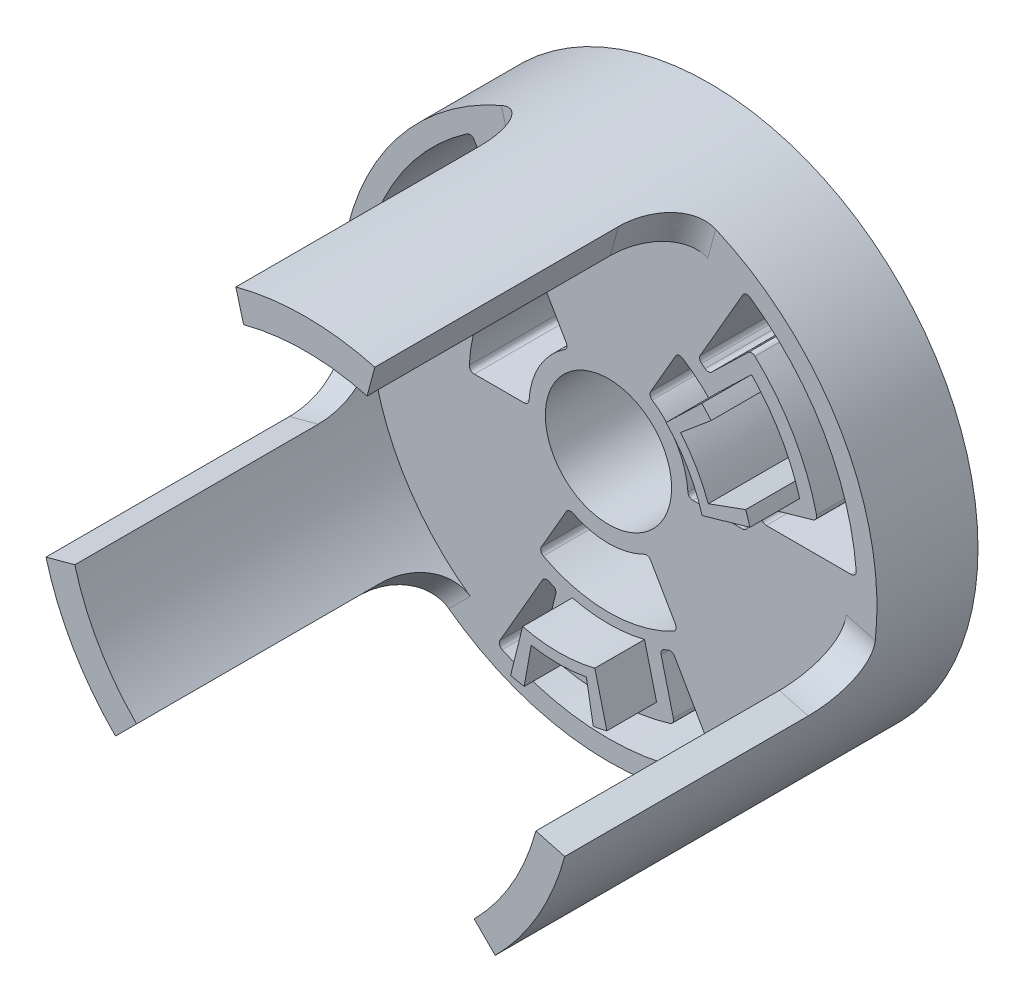
SolidWorks part; units mm, degrees
ref_plane "Front" through (0, 0, 0) normal (0, 0, 1) x (1, 0, 0)
ref_plane "Top" through (0, 0, 0) normal (0, 1, 0) x (1, 0, 0)
ref_plane "Right" through (0, 0, 0) normal (1, 0, 0) x (0, 0, -1)
sketch "Sketch1" plane through (0, 0, 0) normal (0, 0, 1) x (1, 0, 0)
  circle A0 centre (0, 0) radius 13.5
  dimension "D1" = 27
extrude "Boss-Extrude1" add sketch "Sketch1" along normal blind 5.08 contours A0
sketch "Sketch2" plane through (0, 0, 5.08) normal (0, 0, 1) x (1, 0, 0)
  circle A0 centre (0, 0) radius 3.175
  dimension "D1" = 6.35
extrude "Cut-Extrude1" cut sketch "Sketch2" against normal up to surface (5.08 mm away) up to face at (13.5, 0, 0)
sketch "Sketch3" plane through (0, 0, 5.08) normal (0, 0, 1) x (1, 0, 0)
  line L0 (-2, 3.4641) -> (-3.5, 6.0622)
  line L1 (2, 3.4641) -> (3.5, 6.0622)
  line L2 (-4, 0) -> (-7, 0)
  line L3 (-2, -3.4641) -> (-3.5, -6.0622)
  line L4 (2, -3.4641) -> (3.5, -6.0622)
  line L5 (4, 0) -> (7, 0)
  circle A0 centre (0, 0) radius 1.651
  circle A2 centre (0, 0) radius 4
  circle A3 centre (0, 0) radius 7
  dimension "D1" = 3.302
  dimension "D2" = 8
  dimension "D3" = 14
  dimension "D4" = 60
  dimension "D5" = 60
  dimension "D6" = 60
  dimension "D7" = 60
extrude "Cut-Extrude2" cut sketch "Sketch3" against normal up to surface (5.08 mm away) contours L0 A3 L2 A2 | L5 A3 L1 A2 | L3 A3 L4 A2 region at (-4.6612, 2.6912, 5.08) region at (4.6612, 2.6912, 5.08) region at (0, -5.3823, 5.08) up to face at (3.175, 0, 0)
sketch "Sketch5" plane through (0, 0, 5.08) normal (0, 0, 1) x (1, 0, 0)
  line L0 (0, 0) -> (13.9744, -8.0681) construction
  line L1 (0, 0) -> (0, 15.3291) construction
  line L2 (0, 0) -> (-15.9825, -9.2275) construction
  line L3 (2, 3.4641) -> (3.5, 6.0622) construction
  line L4 (4, 0) -> (7, 0) construction
  line L5 (-2, -3.4641) -> (-3.5, -6.0622) construction
  line L6 (-2, 3.4641) -> (-3.5, 6.0622) construction
  line L7 (8.4853, -8.4853) -> (9.5459, -9.5459)
  line L8 (-8.4853, -8.4853) -> (-9.5459, -9.5459)
  line L9 (-3.1058, 11.5911) -> (-3.4941, 13.04)
  line L10 (3.1058, 11.5911) -> (3.4941, 13.04)
  line L11 (11.5911, -3.1058) -> (13.04, -3.4941)
  line L12 (-11.5911, -3.1058) -> (-13.04, -3.4941)
  arc A0 (3.4941, 13.04) -> (-3.4941, 13.04) centre (0, 0) ccw
  arc A1 (3.1058, 11.5911) -> (-3.1058, 11.5911) centre (0, 0) ccw
  arc A2 (9.5459, -9.5459) -> (13.04, -3.4941) centre (0, 0) ccw
  arc A3 (8.4853, -8.4853) -> (11.5911, -3.1058) centre (0, 0) ccw
  arc A4 (-13.04, -3.4941) -> (-9.5459, -9.5459) centre (0, 0) ccw
  arc A5 (-11.5911, -3.1058) -> (-8.4853, -8.4853) centre (0, 0) ccw
  dimension "D1" = 24
  dimension "D2" = 27
  dimension "D7" = 30
  dimension "D3" = 30
  dimension "D4" = 30
  dimension "D5" = 30
  dimension "D6" = 30
  dimension "D8" = 30
  dimension "D9" = 30
extrude "Boss-Extrude3" add sketch "Sketch5" along normal blind 15.24
sketch "Sketch8" plane through (0, 0, 5.08) normal (0, 0, 1) x (1, 0, 0)
  line L0 (0, 0) -> (-17.5986, 10.1605) construction
  line L1 (0, 0) -> (17.4193, 10.057) construction
  line L2 (0, 0) -> (0, -20.3314) construction
  line L3 (5.7547, 5.5573) -> (7.1934, 6.9466)
  line L4 (-4, 0) -> (-7, 0) construction
  line L5 (2, 3.4641) -> (3.5, 6.0622) construction
  line L6 (6.1284, 5.1423) -> (7.2774, 6.1065)
  line L7 (7.5175, 2.7362) -> (8.9271, 3.2492)
  line L8 (7.6901, 2.2051) -> (9.6126, 2.7564)
  line L9 (-7.2774, 6.1065) -> (-6.1284, 5.1423)
  line L10 (-5.7547, 5.5573) -> (-7.1934, 6.9466)
  line L11 (-7.6901, 2.2051) -> (-9.6126, 2.7564)
  line L12 (-8.9271, 3.2492) -> (-7.5175, 2.7362)
  line L13 (-1.3892, -7.8785) -> (-1.6497, -9.3557)
  line L14 (-2.4192, -9.703) -> (-1.9354, -7.7624)
  line L15 (1.3892, -7.8785) -> (1.6497, -9.3557)
  line L16 (2.4192, -9.703) -> (1.9354, -7.7624)
  line L17 (1.6497, -9.3557) -> (1.7365, -9.8481)
  line L18 (-1.6497, -9.3557) -> (-1.7365, -9.8481)
  line L19 (-8.9271, 3.2492) -> (-9.3969, 3.4202)
  line L20 (-7.2774, 6.1065) -> (-7.6604, 6.4279)
  line L21 (8.9271, 3.2492) -> (9.3969, 3.4202)
  line L22 (7.2774, 6.1065) -> (7.6604, 6.4279)
  line L23 (-7.6901, 2.2051) -> (-7.2095, 2.0673)
  line L26 (-5.7547, 5.5573) -> (-5.395, 5.2099)
  line L27 (5.7547, 5.5573) -> (5.395, 5.2099)
  line L30 (7.6901, 2.2051) -> (7.2095, 2.0673)
  line L31 (1.9354, -7.7624) -> (1.8144, -7.2772)
  line L33 (-1.9354, -7.7624) -> (-1.8144, -7.2772)
  arc A1 (-2.4192, -9.703) -> (-1.7365, -9.8481) centre (0, 0) ccw
  arc A6 (9.6126, 2.7564) -> (9.3969, 3.4202) centre (0, 0) ccw
  arc A10 (-7.1934, 6.9466) -> (-7.6604, 6.4279) centre (0, 0) ccw
  arc A12 (1.7365, -9.8481) -> (2.4192, -9.703) centre (0, 0) ccw
  arc A13 (-9.3969, 3.4202) -> (-9.6126, 2.7564) centre (0, 0) ccw
  arc A14 (7.6604, 6.4279) -> (7.1934, 6.9466) centre (0, 0) ccw
  arc A15 (7.2095, 2.0673) -> (5.395, 5.2099) centre (0, 0) ccw
  arc A16 (7.5175, 2.7362) -> (6.1284, 5.1423) centre (0, 0) ccw
  arc A17 (-1.3892, -7.8785) -> (1.3892, -7.8785) centre (0, 0) ccw
  arc A18 (-1.8144, -7.2772) -> (1.8144, -7.2772) centre (0, 0) ccw
  arc A19 (-6.1284, 5.1423) -> (-7.5175, 2.7362) centre (0, 0) ccw
  arc A20 (-5.395, 5.2099) -> (-7.2095, 2.0673) centre (0, 0) ccw
  dimension "D2" = 15
  dimension "D3" = 20
  dimension "D4" = 30
  dimension "D5" = 30
  dimension "D6" = 4
  dimension "D7" = 10
  dimension "D8" = 4
  dimension "D9" = 10
  dimension "D10" = 4
  dimension "D11" = 10
extrude "Boss-Extrude4" add sketch "Sketch8" along normal blind 2.5
sketch "Sketch9" plane through (0, 0, 5.08) normal (0, 0, 1) x (1, 0, 0)
  line L0 (1.3892, -7.8785) -> (1.7365, -9.8481) construction
  line L1 (-1.7365, -9.8481) -> (-1.3892, -7.8785) construction
  line L2 (9.3969, 3.4202) -> (7.5175, 2.7362) construction
  line L3 (6.1284, 5.1423) -> (7.6604, 6.4279) construction
  line L4 (-7.5175, 2.7362) -> (-9.3969, 3.4202) construction
  line L5 (-7.6604, 6.4279) -> (-6.1284, 5.1423) construction
  line L6 (1.3892, -7.8785) -> (1.7365, -9.8481)
  line L7 (-1.7365, -9.8481) -> (-1.3892, -7.8785)
  line L8 (9.3969, 3.4202) -> (7.5175, 2.7362)
  line L9 (6.1284, 5.1423) -> (7.6604, 6.4279)
  line L10 (-7.5175, 2.7362) -> (-9.3969, 3.4202)
  line L11 (-7.6604, 6.4279) -> (-6.1284, 5.1423)
  arc A0 (-1.3892, -7.8785) -> (1.3892, -7.8785) centre (0, 0) ccw construction
  arc A1 (7.5175, 2.7362) -> (6.1284, 5.1423) centre (0, 0) ccw construction
  arc A2 (-6.1284, 5.1423) -> (-7.5175, 2.7362) centre (0, 0) ccw construction
  arc A3 (-1.3892, -7.8785) -> (1.3892, -7.8785) centre (0, 0) ccw
  arc A4 (7.5175, 2.7362) -> (6.1284, 5.1423) centre (0, 0) ccw
  arc A5 (-6.1284, 5.1423) -> (-7.5175, 2.7362) centre (0, 0) ccw
  arc A7 (-7.6604, 6.4279) -> (-9.3969, 3.4202) centre (0, 0) ccw
  arc A8 (9.3969, 3.4202) -> (7.6604, 6.4279) centre (0, 0) ccw
  arc A9 (-1.7365, -9.8481) -> (1.7365, -9.8481) centre (0, 0) ccw
extrude "Cut-Extrude3" cut sketch "Sketch9" against normal up to next
ref_axis "Axis1" through (0, 0, 0) along (0, 0, 1)
fillet "Fillet3" radius 2 6 edges at (-12.3156, -3.2999, 5.08) (-9.0156, -9.0156, 5.08) (9.0156, -9.0156, 5.08) (12.3156, -3.2999, 5.08) (3.2999, 12.3156, 5.08) (-3.2999, 12.3156, 5.08) second distance 3 first distance on face at (0, -9.0072, 5.08)
sketch "Sketch10" plane through (0, 0, 5.08) normal (0, 0, 1) x (1, 0, 0)
  line L0 (-7, 0) -> (-13.5, 0) construction
  line L1 (-3.5, 6.0622) -> (-6.75, 11.6913) construction
  line L11 (-4.5063, 6.3052) -> (-6.8883, 10.4308)
  line L13 (-4.8741, 5.7494) -> (-7.1931, 7.9889)
  line L14 (-10.5151, 2.2349) -> (-7.4162, 1.3463)
  line L15 (-5.0277, 5.8978) -> (-7.1931, 7.9889)
  line L16 (-10.5151, 2.2349) -> (-7.6215, 1.4052)
  line L17 (-4.1495, 5.6872) -> (-7.3995, 11.3163) construction
  line L18 (-7.7136, 0.75) -> (-12.4775, 0.75)
  line L20 (-7, 0.75) -> (-13.5, 0.75) construction
  arc A0 (-3.5, 6.0622) -> (-7, 0) centre (0, 0) ccw construction
  arc A1 (-5.3874, 12.3785) -> (-13.4137, -1.5236) centre (0, 0) ccw construction
  arc A2 (-3.5, 6.0622) -> (-7, 0) centre (0, 0) ccw construction
  arc A3 (-5.3874, 12.3785) -> (-13.4137, -1.5236) centre (0, 0) ccw construction
  arc A11 (-4.5063, 6.3052) -> (-5.0277, 5.8978) centre (0, 0) ccw
  arc A12 (-7.6215, 1.4052) -> (-7.7136, 0.75) centre (0, 0) ccw
  arc A13 (-6.8883, 10.4308) -> (-12.4775, 0.75) centre (0, 0) ccw
  arc A14 (-7.1931, 7.9889) -> (-8.235, 6.91) centre (0, 0) ccw
  arc A15 (-10.1017, 3.6767) -> (-10.5151, 2.2349) centre (0, 0) ccw
  arc A16 (-8.235, 6.91) -> (-10.1017, 3.6767) centre (0, 0) ccw
  arc A17 (-7.1931, 7.9889) -> (-8.235, 6.91) centre (0, 0) ccw
  arc A18 (-10.1017, 3.6767) -> (-10.5151, 2.2349) centre (0, 0) ccw
  arc A19 (-8.235, 6.91) -> (-10.1017, 3.6767) centre (0, 0) ccw
  arc A20 (-3.875, 6.7117) -> (-7.75, 0) centre (0, 0) ccw construction
  dimension "D3" = 1
  dimension "D6" = 12.5
  dimension "D1" = 0.75
  dimension "D2" = 0.75
  dimension "D4" = 0.75
  dimension "D5" = 0.75
extrude "Cut-Extrude4" cut sketch "Sketch10" against normal up to next contours A13 L18 A12 L16 A18 A19 A17 L15 A11 L11
fillet "Fillet4" radius 0.25 20 edges at (-7.6215, 1.4052, 2.54) (-7.7136, 0.75, 2.54) (-10.5151, 2.2349, 2.54) (-12.4775, 0.75, 2.54) (-4.5063, 6.3052, 2.54) (-5.0277, 5.8978, 2.54) (-6.8883, 10.4308, 2.54) (-7.1931, 7.9889, 2.54) (-7, 0, 2.54) (-4, 0, 2.54) (-2, 3.4641, 2.54) (-3.5, 6.0622, 2.54) (-3.5, -6.0622, 2.54) (-2, -3.4641, 2.54) (3.5, -6.0622, 2.54) (2, -3.4641, 2.54) (4, 0, 2.54) (2, 3.4641, 2.54) (7, 0, 2.54) (3.5, 6.0622, 2.54)
pattern_circular "CirPattern1" count 3 over 360 about axis through (0, 0, 0) along (0, 0, 1) of "Cut-Extrude4", "Fillet4"
